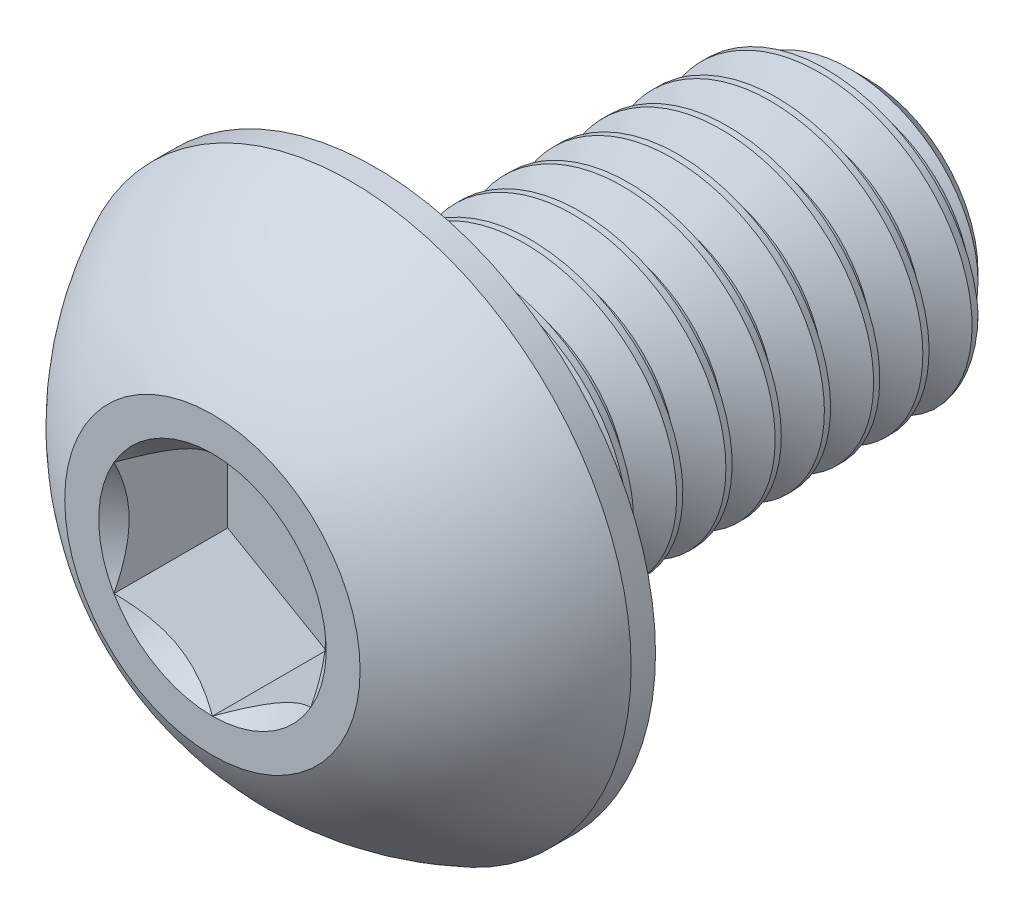
SolidWorks part; units mm, degrees
ref_plane "Front" through (0, 0, 0) normal (0, 0, 1) x (1, 0, 0)
ref_plane "Top" through (0, 0, 0) normal (0, 1, 0) x (1, 0, 0)
ref_plane "Right" through (0, 0, 0) normal (1, 0, 0) x (0, 0, -1)
sketch "Sketch1" plane through (0, 0, 0) normal (1, 0, 0) x (0, 0, -1)
  line L2 (1.65, 1.5) -> (6.65, 1.5)
  line L3 (6.65, 1.5) -> (6.65, 0)
  line L4 (6.65, 0) -> (1.65, 0)
  line L6 (1.4025, 2.85) -> (1.65, 2.85) construction
  line L7 (6.65, 1.5) -> (6.65, -1.5) construction
  line L8 (0, 0) -> (1.65, 0) construction
  line L9 (1.65, 2.85) -> (1.65, -2.85) construction
  line L11 (1.65, 1.5) -> (1.65, 0)
  line L13 (0, 1) -> (0, -1) construction
  line L14 (0, 1) -> (0, 1.5) construction
  line L15 (6.65, -1.5) -> (6.15, -1.5) construction
  arc A3 (0, 1.5) -> (1.4025, 2.85) centre (2.7948, 0) cw construction
  dimension "D1" = 0.2475
  dimension "Pitch" = 0.5
revolve "Revolve1" add sketch "Sketch1" angle 360 mid plane about L4
sketch "Sketch7" plane through (0, 0, 0) normal (1, 0, 0) x (0, 0, -1)
  line L6 (1.4025, 2.85) -> (1.65, 2.85) construction
  line L8 (0, 0) -> (1.65, 0) construction
  line L11 (1.65, 2.85) -> (1.65, -2.85) construction
  line L12 (1.4025, 2.85) -> (1.65, 2.85)
  line L13 (0, 0) -> (1.65, 0)
  line L14 (0, 1) -> (0, -1) construction
  line L15 (1.65, 2.85) -> (1.65, 0)
  line L16 (0, 1.5) -> (0, 0)
  arc A2 (1.4025, 2.85) -> (0, 1.5) centre (2.7948, 0) ccw construction
  arc A3 (1.4025, 2.85) -> (0, 1.5) centre (2.7948, 0) ccw
revolve "Revolve2" add sketch "Sketch7" angle 360 mid plane about L13
sketch "Sketch5" plane through (0, 0, 0) normal (0, 0, 1) x (1, 0, 0)
  line L1 (1, -0.5774) -> (1, 0.5774)
  line L2 (1, 0.5774) -> (0, 1.1547)
  line L3 (0, 1.1547) -> (-1, 0.5774)
  line L4 (-1, 0.5774) -> (-1, -0.5774)
  line L5 (-1, -0.5774) -> (0, -1.1547)
  line L6 (0, -1.1547) -> (1, -0.5774)
  circle A0 centre (0, 0) radius 1 construction
extrude "Cut-Extrude2" cut sketch "Sketch5" against normal blind 1.155
sketch "Sketch6" plane through (0, 0, 0) normal (0, 0, 1) x (1, 0, 0)
  circle A0 centre (0, 0) radius 1.1547
extrude "Cut-Extrude3" cut sketch "Sketch6" against normal blind 1.155 draft 45
sketch "Sketch11" plane through (0, 0, 0) normal (1, 0, 0) x (0, 0, -1)
  line L0 (1.65, -2.85) -> (1.65, 2.85)
  point P4 (1.65, 0)
split "Split1" trim tools "Sketch11" bodies to split 113 resulting bodies 119 120
sketch "Sketch10" plane through (0, 0, 0) normal (1, 0, 0) x (0, 0, -1)
  line L0 (6.65, 1.5) -> (6.65, -1.5) construction
  point P0 (5.9, -1.5)
  dimension "D1" = 0.75
sketch "Sketch3" plane through (0, 0, -6.65) normal (0, 0, -1) x (-1, 0, 0)
  circle A0 centre (0, 0) radius 1.5
curve "Helix/Spiral1" pitch 0.5 height 5.5 turns 11
sketch "Sketch2" plane through (0, 0, 0) normal (1, 0, 0) x (0, 0, -1)
  line L0 (6.6187, 1.5541) -> (7.1187, 1.5541) construction
  line L1 (7.1187, 1.5541) -> (6.8687, 1.1211) construction
  line L2 (6.8687, 1.1211) -> (6.6187, 1.5541) construction
  line L3 (6.8687, 1.5541) -> (6.8687, 1.5) construction
  line L4 (6.8687, 1.5) -> (6.8687, 1.1752) construction
  line L5 (6.8687, 1.1752) -> (6.8687, 1.1211) construction
  line L6 (6.8375, 1.1752) -> (6.9, 1.1752)
  line L7 (6.65, 1.5) -> (7.0875, 1.5) construction
  line L8 (6.6344, 1.5271) -> (7.1031, 1.5271)
  line L9 (6.6344, 1.5271) -> (6.8375, 1.1752)
  line L10 (7.1031, 1.5271) -> (6.9, 1.1752)
  point P10 (6.8687, 1.1752)
  point P13 (6.8687, 1.5)
  point P16 (6.8687, 1.5271)
  dimension "D1" = 0.5
  dimension "D2" = 0.0625
chamfer "Chamfer1" distance 0.375 angle 45 1 edges at (0, 1.5, -6.65)
sweep "Cut-Sweep1" cut profiles "Sketch2" path "Helix/Spiral1" align with end faces yes
combine bodies "Combine1" operation type add bodies to combine 120 114
equation "\"D3@Helix/Spiral1\" = \"Lg@Sketch1\" + \"D4@Helix/Spiral1\""
equation "\"D1@Chamfer1\" = \"D4@Helix/Spiral1\" * .75"
equation "\"D1@Cut-Extrude2\" = \"Head Ht@Sketch1\" * .7"
equation "\"D1@Sketch1\" = \"Head Ht@Sketch1\" * .15"
equation "\"D1@Sketch10\" = \"D4@Helix/Spiral1\" * 1.5"
equation "\"D1@Cut-Extrude3\" = \"D1@Cut-Extrude2\""
equation "\"D4@Helix/Spiral1\"=\"Pitch@Sketch1\""
equation "\"D1@Sketch2\"=\"Pitch@Sketch1\""
equation "\"D2@Sketch2\"=\"D1@Sketch2\"/8"
